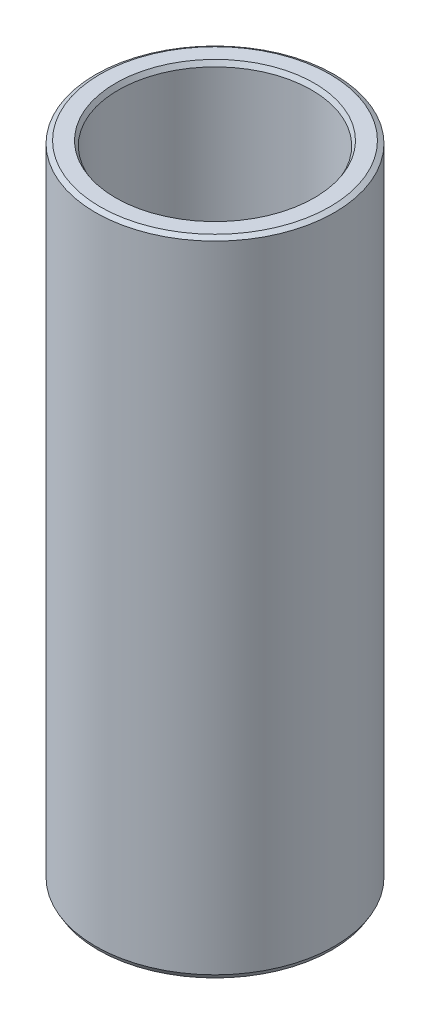
SolidWorks part; units mm, degrees
ref_plane "Front Plane" through (0, 0, 0) normal (0, 0, 1) x (1, 0, 0)
ref_plane "Top Plane" through (0, 0, 0) normal (0, 1, 0) x (1, 0, 0)
ref_plane "Right Plane" through (0, 0, 0) normal (1, 0, 0) x (0, 0, -1)
sketch "Sketch1" plane through (0, 0, 0) normal (0, 1, 0) x (1, 0, 0)
  circle A0 centre (0, 0) radius 52.5
  dimension "SLEEVE_OD" = 105
extrude "Boss-Extrude1" add sketch "Sketch1" along normal blind 282.3681
sketch "Sketch2" plane through (0, 0, 0) normal (0, 1, 0) x (1, 0, 0)
  circle A0 centre (0, 0) radius 42.4848
  dimension "BORE_D" = 84.9696
extrude "Cut-Extrude1" cut sketch "Sketch2" along normal through all
chamfer "Chamfer1" distance 1.1701 angle 60 4 edges at (0, 282.3681, 42.4848) (0, 0, 42.4848) (0, 0, 52.5) (0, 282.3681, 52.5) first distance on face at (0, 282.3681, 42.4848) first distance on face at (0, 0, 42.4848) first distance on face at (0, 282.3681, 52.5)
